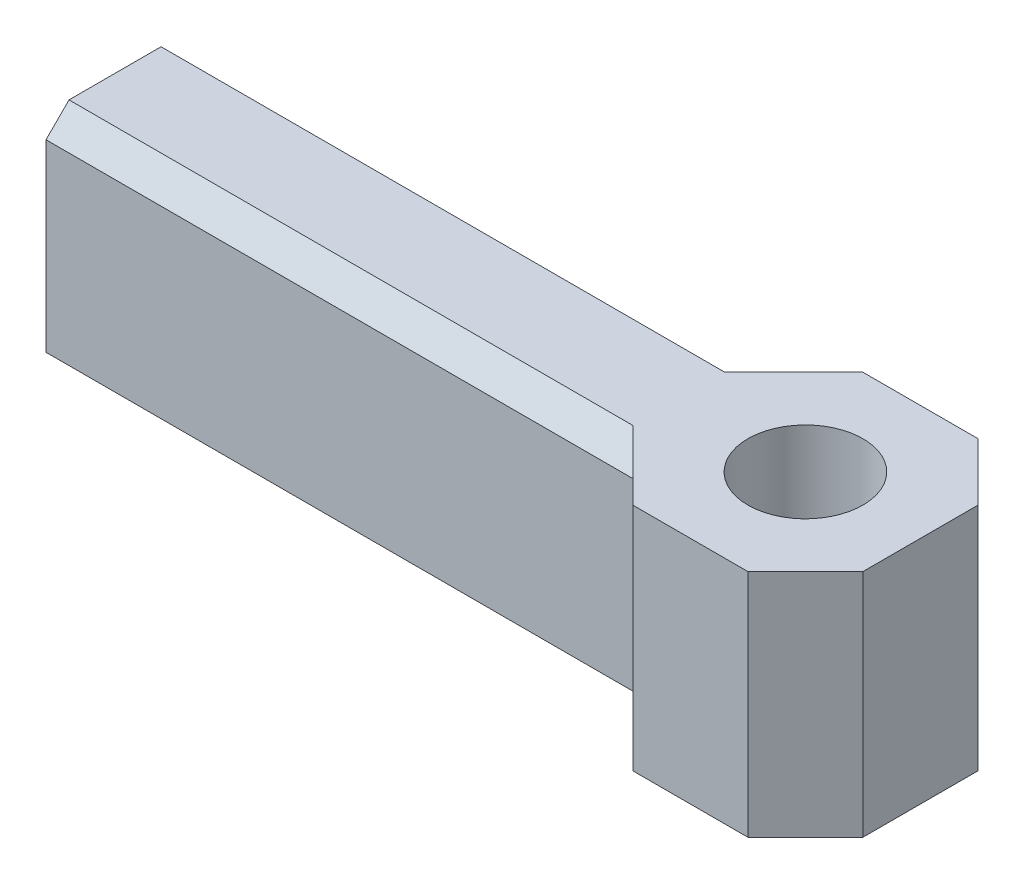
SolidWorks part; units mm, degrees
ref_plane "Front Plane" through (0, 0, 0) normal (0, 0, 1) x (1, 0, 0)
ref_plane "Top Plane" through (0, 0, 0) normal (0, 1, 0) x (1, 0, 0)
ref_plane "Right Plane" through (0, 0, 0) normal (1, 0, 0) x (0, 0, -1)
sketch "Sketch1" plane through (0, 0, 0) normal (0, 1, 0) x (1, 0, 0)
  line L0 (-5, 5) -> (-5, 3)
  line L1 (-5, -5) -> (5, -5)
  line L2 (-5, -5) -> (-5, 5) construction
  line L3 (-5, 5) -> (5, 5)
  line L4 (5, -5) -> (5, 5)
  line L5 (-5, -5) -> (5, 5) construction
  line L6 (-5, 5) -> (5, -5) construction
  line L7 (-5, 3) -> (-30, 3)
  line L8 (-30, 3) -> (-30, -3)
  line L9 (-30, -3) -> (-5, -3)
  line L10 (-5, -3) -> (-5, -5)
  line L11 (-30, 0) -> (28.5868, 0) construction
  point P0 (0, 0)
  dimension "D1" = 6
  dimension "D2" = 10
  dimension "D3" = 10
  dimension "D4" = 25
extrude "Boss-Extrude1" add sketch "Sketch1" along normal blind 10
sketch "Sketch2" plane through (0, 10, 0) normal (0, 1, 0) x (1, 0, 0)
  circle A0 centre (0, 0) radius 2.5
  dimension "D1" = 5
extrude "Cut-Extrude1" cut sketch "Sketch2" against normal blind 10
sketch "Sketch4" plane through (-30, 0, 0) normal (-1, 0, 0) x (0, 0, 1)
  line L0 (-3, 0) -> (3, 10) construction
  line L1 (3, 10) -> (3, 0) construction
  line L2 (3, 0) -> (-3, 10) construction
  circle A0 centre (0, 5) radius 1.7
  dimension "D1" = 3.4
extrude "Cut-Extrude4" cut sketch "Sketch4" against normal blind 20
chamfer "Chamfer1" distance 2.5 angle 45 4 edges at (5, 5, -5) (5, 5, 5) (-5, 5, 5) (-5, 5, -5)
chamfer "Chamfer2" distance 1 angle 45 4 edges at (-17.25, 0, 3) (-17.25, 10, 3) (-17.25, 0, -3) (-17.25, 10, -3)
